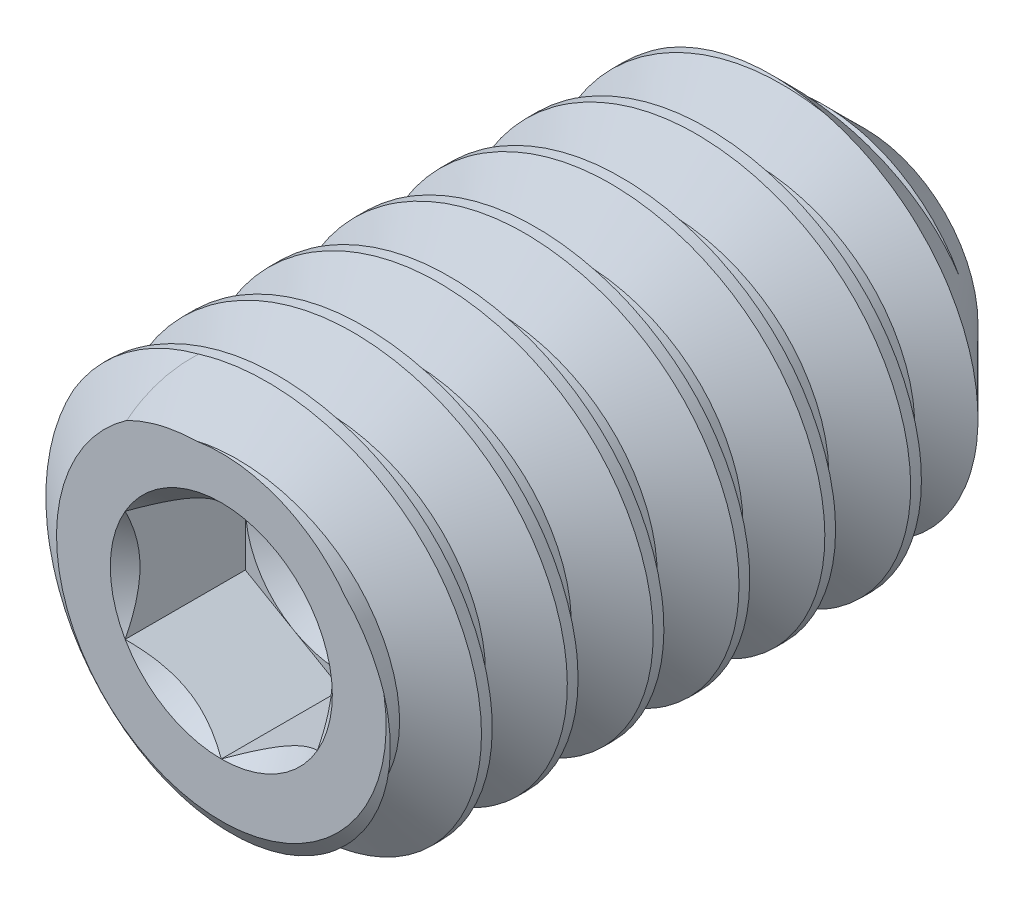
SolidWorks part; units mm, degrees
ref_plane "Front" through (0, 0, 0) normal (0, 0, 1) x (1, 0, 0)
ref_plane "Top" through (0, 0, 0) normal (0, 1, 0) x (1, 0, 0)
ref_plane "Right" through (0, 0, 0) normal (1, 0, 0) x (0, 0, -1)
sketch "Sketch22" plane through (0, 0, 0) normal (1, 0, 0) x (0, 0, -1)
  line L0 (-1.0652, 0) -> (-1.0652, 0.6096)
  line L1 (-1.0652, 0.6096) -> (-0.9585, 0.762)
  line L2 (-0.9585, 0.762) -> (0.9716, 0.762)
  line L3 (0.9716, 0.762) -> (1.3161, 0.4175)
  line L4 (1.3161, 0.4175) -> (1.0652, 0)
  line L5 (1.0652, 0) -> (-1.0652, 0)
  line L6 (1.0652, 0) -> (1.3161, 0) construction
  line L7 (1.3161, 0) -> (1.3161, 0.4175) construction
  line L8 (1.3161, -0.4175) -> (1.0652, 0) construction
  line L9 (-0.9585, -0.762) -> (0.9716, -0.762) construction
  dimension "Dia" = 1.524
  dimension "Length" = 2.3813
  dimension "D3" = 35
  dimension "D5" = 118
  dimension "D6" = 45
  dimension "D7" = 1.2192
revolve "Revolve1" add sketch "Sketch22" angle 360 about L6
ref_plane "Plane1" through (0, 0, -1.3161) normal (0, 0, 1) x (1, 0, 0)
sketch "Sketch27" plane through (0, 0, -1.3161) normal (0, 0, 1) x (1, 0, 0)
  circle A0 centre (0, 0) radius 0.762 construction
  circle A1 centre (0, 0) radius 0.762
curve "Helix/Spiral1" pitch 0.3175 height 2.9527 radius 0.762 centre (0, 0, -1.3161) axis (0, 0, 1) start towards (0, 1, 0)
sketch "Sketch28" plane through (0, 0, 0) normal (1, 0, 0) x (0, 0, -1)
  line L0 (1.3161, 0.762) -> (1.5939, 0.762)
  line L1 (1.5939, 0.762) -> (1.4828, 0.5695)
  line L2 (1.4828, 0.5695) -> (1.4272, 0.5695)
  line L3 (1.4272, 0.5695) -> (1.3161, 0.762)
  line L4 (1.3716, 0.6658) -> (1.5383, 0.6658) construction
  line L6 (-0.9585, 0.762) -> (0.9716, 0.762) construction
  line L7 (1.3161, 0.852) -> (1.3161, -0.852) construction
  dimension "D1" = 0.0556
  dimension "D3" = 60
  dimension "D2" = 0.2778
sweep "Cut-Sweep2" cut profiles "Sketch28" path "Helix/Spiral1" align with end faces yes
sketch "Sketch23" plane through (0, 0, 1.0652) normal (0, 0, 1) x (1, 0, 0)
  line L1 (0, 0.4106) -> (-0.3556, 0.2053)
  line L2 (-0.3556, 0.2053) -> (-0.3556, -0.2053)
  line L3 (-0.3556, -0.2053) -> (0, -0.4106)
  line L4 (0, -0.4106) -> (0.3556, -0.2053)
  line L5 (0.3556, -0.2053) -> (0.3556, 0.2053)
  line L6 (0.3556, 0.2053) -> (0, 0.4106)
  circle A0 centre (0, 0) radius 0.3556 construction
  dimension "Hex" = 0.7112
extrude "Cut-Extrude10" cut sketch "Sketch23" against normal blind 0.4445
sketch "Sketch24" plane through (0, 0, 1.0652) normal (0, 0, 1) x (1, 0, 0)
  circle A0 centre (0, 0) radius 0.4106
extrude "Cut-Extrude11" cut sketch "Sketch24" against normal through all draft 45
sketch "Sketch26" plane through (0, 0, 0.6207) normal (0, 0, 1) x (1, 0, 0)
  circle A0 centre (0, 0) radius 0.3556 construction
  circle A1 centre (0, 0) radius 0.3556
extrude "Cut-Extrude12" cut sketch "Sketch26" against normal through all draft 60
sketch "Sketch30" plane through (0, 0, 0) normal (1, 0, 0) x (0, 0, -1)
  line L0 (-0.9585, 0.762) -> (0.9716, 0.762) construction
  line L1 (-1.0652, 0) -> (-1.0652, 0.6096) construction
  line L2 (1.3161, 0) -> (1.3161, 0.4175) construction
  line L3 (-0.9585, -0.762) -> (0.9716, -0.762) construction
  point P0 (-1.0652, 0.762)
  point P1 (1.3161, 0.762)
  point P2 (1.3161, -0.762)
  point P11 (0.5223, -0.762)
  dimension "D1" = 0.7937
sketch "Sketch31" plane through (0, 0, 0) normal (1, 0, 0) x (0, 0, -1)
  line L2 (1.0652, 0) -> (1.3161, -0.4175)
  line L3 (1.3161, 0.4175) -> (1.0652, 0)
equation "\"D7@Sketch22\"=\"Dia@Sketch22\"*.8"
equation "\"D1@Sketch28\" = \"D4@Helix/Spiral1\" * .175"
equation "\"D3@Helix/Spiral1\" = \"Length@Sketch22\" + \"D4@Helix/Spiral1\" + .01"
equation "\"D1@Sketch30\" = \"D4@Helix/Spiral1\" * 2.5"
equation "\"hex Depth@Cut-Extrude10\" = \"Hex@Sketch23\" * .625"
equation "\"D2@Sketch28\" = \"D4@Helix/Spiral1\" * .875"
